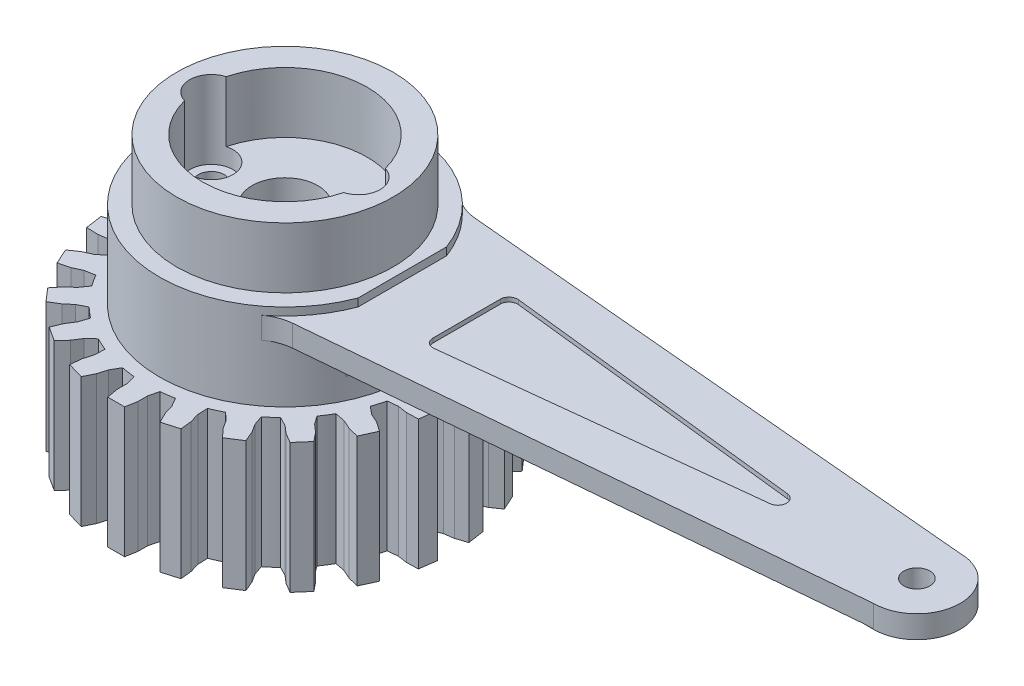
SolidWorks part; units mm, degrees
other "Markup1"
sketch "Sketch11" plane through (-17.3474, -40, -17.5082) normal (-0.1763, -0.9804, -0.0883) x (-0.1909, 0.1221, -0.974)
ref_plane "Front Plane" through (0, 0, 0) normal (0, 0, 1) x (1, 0, 0)
ref_plane "Top Plane" through (0, 0, 0) normal (0, 1, 0) x (1, 0, 0)
ref_plane "Right Plane" through (0, 0, 0) normal (1, 0, 0) x (0, 0, -1)
sketch "Sketch1" plane through (0, 0, 0) normal (0, 1, 0) x (1, 0, 0)
  circle A0 centre (0, 0) radius 14.5
extrude "Boss-Extrude1" add sketch "Sketch1" along normal blind 2 contours A0
sketch "Sketch2" plane through (0, 2, 0) normal (0, 1, 0) x (1, 0, 0)
  line L0 (0, 0) -> (-8.5, 0) construction
  line L1 (0, 0) -> (0, -2.0986) construction
  circle A0 centre (0, 0) radius 3.8
  circle A1 centre (-8.5, 0) radius 1.5
  circle A2 centre (8.5, 0) radius 1.5
  dimension "D1" = 8.5
extrude "Cut-Extrude1" cut sketch "Sketch2" against normal blind 2.5
sketch "Sketch3" plane through (0, 0, 0) normal (0, -1, 0) x (1, 0, 0)
  circle A0 centre (0, 0) radius 14.5
  circle A1 centre (0, 0) radius 12.5
  circle M3 centre (8.5, 0) radius 1.5
  circle M4 centre (-8.5, 0) radius 1.5
  circle M5 centre (0, 0) radius 3.8
  dimension "D1" = 2
extrude "Boss-Extrude2" add sketch "Sketch3" along normal blind 7 contours A1 M3 M5 M4 | A0 region at (-12.1464, 0, 0)
sketch "Sketch4" plane through (0, 2, 0) normal (0, 1, 0) x (1, 0, 0)
  circle A0 centre (0, 0) radius 3.8
  circle A1 centre (8.5, 0) radius 1.5
  circle A2 centre (-8.5, 0) radius 1.5
  circle A3 centre (0, 0) radius 14.5
extrude "Boss-Extrude3" add sketch "Sketch4" along normal blind 1 contours A3 | A2 | A1 | A0
sketch "Sketch5" plane through (0, 3, 0) normal (0, 1, 0) x (1, 0, 0)
  line L0 (0, 0) -> (0, 9.3425) construction
  circle A0 centre (8.5, 0) radius 2.6
  circle A1 centre (-8.5, 0) radius 2.5
extrude "Cut-Extrude2" cut sketch "Sketch5" against normal blind 2
sketch "Sketch6" plane through (0, 3, 0) normal (0, 1, 0) x (1, 0, 0)
  line L0 (0, 0) -> (30, 0) construction
  line L1 (30, 0) -> (45, 0) construction
  line L2 (45, 0) -> (60, 0) construction
  line L3 (60, 5) -> (13.6107, 5)
  line L4 (60, -5) -> (13.6107, -5)
  line L5 (60, 0) -> (73, 0) construction
  line L6 (60, 5) -> (70, 5)
  line L7 (60, -5) -> (70, -5)
  line L8 (70, 5) -> (73, 5)
  line L9 (70, -5) -> (73, -5)
  circle A4 centre (0, 0) radius 14.5 construction
  circle A6 centre (73, 0) radius 1.5
  arc A8 (73, -5) -> (73, 5) centre (73, 0) ccw
  circle M3 centre (0, 0) radius 14.5
  dimension "D1" = 15
  dimension "D2" = 15
  dimension "D3" = 30
  dimension "D4" = 13
extrude "Boss-Extrude4" add sketch "Sketch6" against normal blind 3.5 contours L4 L3 M3 region at (45.2639, 3, 0)
sketch "Sketch9" plane through (0, -7, 0) normal (0, -1, 0) x (-1, 0, 0)
  line L0 (0, 15.9926) -> (0, 19.4946) construction
  line L1 (0.9773, 19.4946) -> (-0.9773, 19.4946)
  line L2 (-0.9773, 19.4946) -> (-1.2082, 18.1848)
  line L45 (-0.9773, 19.4946) -> (-0.9773, 18.0837) construction
  line L46 (-1.2082, 18.1848) -> (-1.2082, 17.0658)
  line L47 (-1.2082, 17.0658) -> (-1.4932, 15.9228)
  line L48 (-1.2082, 17.0658) -> (-1.2082, 16.2048) construction
  line L49 (1.2082, 17.0658) -> (1.4932, 15.9228)
  line L50 (1.2082, 18.1848) -> (1.2082, 17.0658)
  line L51 (0.9773, 19.4946) -> (1.2082, 18.1848)
  line L52 (5.9673, 16.0341) -> (5.9187, 14.8571)
  line L53 (6.2825, 17.1078) -> (5.9673, 16.0341)
  line L54 (6.4299, 18.4296) -> (6.2825, 17.1078)
  line L55 (6.4299, 18.4296) -> (4.5546, 18.9802)
  line L56 (4.5546, 18.9802) -> (3.964, 17.7886)
  line L57 (3.964, 17.7886) -> (3.6487, 16.7149)
  line L58 (3.6487, 16.7149) -> (3.0533, 15.6985)
  line L59 (10.2429, 13.7034) -> (9.8646, 12.5878)
  line L60 (10.8478, 14.6448) -> (10.2429, 13.7034)
  line L61 (11.3617, 15.8715) -> (10.8478, 14.6448)
  line L62 (11.3617, 15.8715) -> (9.7174, 16.9282)
  line L63 (9.7174, 16.9282) -> (8.815, 15.9512)
  line L64 (8.815, 15.9512) -> (8.21, 15.0098)
  line L65 (8.21, 15.0098) -> (7.3523, 14.2024)
  line L66 (13.6887, 10.2626) -> (13.0115, 9.2987)
  line L67 (14.5343, 10.9954) -> (13.6887, 10.2626)
  line L68 (15.373, 12.0277) -> (14.5343, 10.9954)
  line L69 (15.373, 12.0277) -> (14.093, 13.5048)
  line L70 (14.093, 13.5048) -> (12.9519, 12.8216)
  line L71 (12.9519, 12.8216) -> (12.1062, 12.0888)
  line L72 (12.1062, 12.0888) -> (11.0558, 11.5557)
  line L73 (16.0255, 5.9904) -> (15.1042, 5.2563)
  line L74 (17.0434, 6.4552) -> (16.0255, 5.9904)
  line L75 (18.1389, 7.2094) -> (17.0434, 6.4552)
  line L76 (18.1389, 7.2094) -> (17.3269, 8.9873)
  line L77 (17.3269, 8.9873) -> (16.0395, 8.6533)
  line L78 (16.0395, 8.6533) -> (15.0217, 8.1884)
  line L79 (15.0217, 8.1884) -> (13.8636, 7.9728)
  line L80 (17.064, 1.2328) -> (15.9732, 0.7881)
  line L81 (18.1716, 1.3921) -> (17.064, 1.2328)
  line L82 (19.4352, 1.8071) -> (18.1716, 1.3921)
  line L83 (19.4352, 1.8071) -> (19.1571, 3.7417)
  line L84 (19.1571, 3.7417) -> (17.8277, 3.7839)
  line L85 (17.8277, 3.7839) -> (16.7201, 3.6246)
  line L86 (16.7201, 3.6246) -> (15.5482, 3.744)
  line L87 (16.7201, -3.6246) -> (15.5482, -3.744)
  line L88 (17.8277, -3.7839) -> (16.7201, -3.6246)
  line L89 (19.1571, -3.7417) -> (17.8277, -3.7839)
  line L90 (19.1571, -3.7417) -> (19.4352, -1.8071)
  line L91 (19.4352, -1.8071) -> (18.1716, -1.3921)
  line L92 (18.1716, -1.3921) -> (17.064, -1.2328)
  line L93 (17.064, -1.2328) -> (15.9732, -0.7881)
  line L94 (15.0217, -8.1884) -> (13.8636, -7.9728)
  line L95 (16.0395, -8.6533) -> (15.0217, -8.1884)
  line L96 (17.3269, -8.9873) -> (16.0395, -8.6533)
  line L97 (17.3269, -8.9873) -> (18.1389, -7.2094)
  line L98 (18.1389, -7.2094) -> (17.0434, -6.4552)
  line L99 (17.0434, -6.4552) -> (16.0255, -5.9904)
  line L100 (16.0255, -5.9904) -> (15.1042, -5.2563)
  line L101 (12.1062, -12.0888) -> (11.0558, -11.5557)
  line L102 (12.9519, -12.8216) -> (12.1062, -12.0888)
  line L103 (14.093, -13.5048) -> (12.9519, -12.8216)
  line L104 (14.093, -13.5048) -> (15.373, -12.0277)
  line L105 (15.373, -12.0277) -> (14.5343, -10.9954)
  line L106 (14.5343, -10.9954) -> (13.6887, -10.2626)
  line L107 (13.6887, -10.2626) -> (13.0115, -9.2987)
  line L108 (8.21, -15.0098) -> (7.3523, -14.2024)
  line L109 (8.815, -15.9512) -> (8.21, -15.0098)
  line L110 (9.7174, -16.9282) -> (8.815, -15.9512)
  line L111 (9.7174, -16.9282) -> (11.3617, -15.8715)
  line L112 (11.3617, -15.8715) -> (10.8478, -14.6448)
  line L113 (10.8478, -14.6448) -> (10.2429, -13.7034)
  line L114 (10.2429, -13.7034) -> (9.8646, -12.5878)
  line L115 (3.6487, -16.7149) -> (3.0533, -15.6985)
  line L116 (3.964, -17.7886) -> (3.6487, -16.7149)
  line L117 (4.5546, -18.9802) -> (3.964, -17.7886)
  line L118 (4.5546, -18.9802) -> (6.4299, -18.4296)
  line L119 (6.4299, -18.4296) -> (6.2825, -17.1078)
  line L120 (6.2825, -17.1078) -> (5.9673, -16.0341)
  line L121 (5.9673, -16.0341) -> (5.9187, -14.8571)
  line L122 (-1.2082, -17.0658) -> (-1.4932, -15.9228)
  line L123 (-1.2082, -18.1848) -> (-1.2082, -17.0658)
  line L124 (-0.9773, -19.4946) -> (-1.2082, -18.1848)
  line L125 (-0.9773, -19.4946) -> (0.9773, -19.4946)
  line L126 (0.9773, -19.4946) -> (1.2082, -18.1848)
  line L127 (1.2082, -18.1848) -> (1.2082, -17.0658)
  line L128 (1.2082, -17.0658) -> (1.4932, -15.9228)
  line L129 (-5.9673, -16.0341) -> (-5.9187, -14.8571)
  line L130 (-6.2825, -17.1078) -> (-5.9673, -16.0341)
  line L131 (-6.4299, -18.4296) -> (-6.2825, -17.1078)
  line L132 (-6.4299, -18.4296) -> (-4.5546, -18.9802)
  line L133 (-4.5546, -18.9802) -> (-3.964, -17.7886)
  line L134 (-3.964, -17.7886) -> (-3.6487, -16.7149)
  line L135 (-3.6487, -16.7149) -> (-3.0533, -15.6985)
  line L136 (-10.2429, -13.7034) -> (-9.8646, -12.5878)
  line L137 (-10.8478, -14.6448) -> (-10.2429, -13.7034)
  line L138 (-11.3617, -15.8715) -> (-10.8478, -14.6448)
  line L139 (-11.3617, -15.8715) -> (-9.7174, -16.9282)
  line L140 (-9.7174, -16.9282) -> (-8.815, -15.9512)
  line L141 (-8.815, -15.9512) -> (-8.21, -15.0098)
  line L142 (-8.21, -15.0098) -> (-7.3523, -14.2024)
  line L143 (-13.6887, -10.2626) -> (-13.0115, -9.2987)
  line L144 (-14.5343, -10.9954) -> (-13.6887, -10.2626)
  line L145 (-15.373, -12.0277) -> (-14.5343, -10.9954)
  line L146 (-15.373, -12.0277) -> (-14.093, -13.5048)
  line L147 (-14.093, -13.5048) -> (-12.9519, -12.8216)
  line L148 (-12.9519, -12.8216) -> (-12.1062, -12.0888)
  line L149 (-12.1062, -12.0888) -> (-11.0558, -11.5557)
  line L150 (-16.0255, -5.9904) -> (-15.1042, -5.2563)
  line L151 (-17.0434, -6.4552) -> (-16.0255, -5.9904)
  line L152 (-18.1389, -7.2094) -> (-17.0434, -6.4552)
  line L153 (-18.1389, -7.2094) -> (-17.3269, -8.9873)
  line L154 (-17.3269, -8.9873) -> (-16.0395, -8.6533)
  line L155 (-16.0395, -8.6533) -> (-15.0217, -8.1884)
  line L156 (-15.0217, -8.1884) -> (-13.8636, -7.9728)
  line L157 (-17.064, -1.2328) -> (-15.9732, -0.7881)
  line L158 (-18.1716, -1.3921) -> (-17.064, -1.2328)
  line L159 (-19.4352, -1.8071) -> (-18.1716, -1.3921)
  line L160 (-19.4352, -1.8071) -> (-19.1571, -3.7417)
  line L161 (-19.1571, -3.7417) -> (-17.8277, -3.7839)
  line L162 (-17.8277, -3.7839) -> (-16.7201, -3.6246)
  line L163 (-16.7201, -3.6246) -> (-15.5482, -3.744)
  line L164 (-16.7201, 3.6246) -> (-15.5482, 3.744)
  line L165 (-17.8277, 3.7839) -> (-16.7201, 3.6246)
  line L166 (-19.1571, 3.7417) -> (-17.8277, 3.7839)
  line L167 (-19.1571, 3.7417) -> (-19.4352, 1.8071)
  line L168 (-19.4352, 1.8071) -> (-18.1716, 1.3921)
  line L169 (-18.1716, 1.3921) -> (-17.064, 1.2328)
  line L170 (-17.064, 1.2328) -> (-15.9732, 0.7881)
  line L171 (-15.0217, 8.1884) -> (-13.8636, 7.9728)
  line L172 (-16.0395, 8.6533) -> (-15.0217, 8.1884)
  line L173 (-17.3269, 8.9873) -> (-16.0395, 8.6533)
  line L174 (-17.3269, 8.9873) -> (-18.1389, 7.2094)
  line L175 (-18.1389, 7.2094) -> (-17.0434, 6.4552)
  line L176 (-17.0434, 6.4552) -> (-16.0255, 5.9904)
  line L177 (-16.0255, 5.9904) -> (-15.1042, 5.2563)
  line L178 (-12.1062, 12.0888) -> (-11.0558, 11.5557)
  line L179 (-12.9519, 12.8216) -> (-12.1062, 12.0888)
  line L180 (-14.093, 13.5048) -> (-12.9519, 12.8216)
  line L181 (-14.093, 13.5048) -> (-15.373, 12.0277)
  line L182 (-15.373, 12.0277) -> (-14.5343, 10.9954)
  line L183 (-14.5343, 10.9954) -> (-13.6887, 10.2626)
  line L184 (-13.6887, 10.2626) -> (-13.0115, 9.2987)
  line L185 (-8.21, 15.0098) -> (-7.3523, 14.2024)
  line L186 (-8.815, 15.9512) -> (-8.21, 15.0098)
  line L187 (-9.7174, 16.9282) -> (-8.815, 15.9512)
  line L188 (-9.7174, 16.9282) -> (-11.3617, 15.8715)
  line L189 (-11.3617, 15.8715) -> (-10.8478, 14.6448)
  line L190 (-10.8478, 14.6448) -> (-10.2429, 13.7034)
  line L191 (-10.2429, 13.7034) -> (-9.8646, 12.5878)
  line L192 (-3.6487, 16.7149) -> (-3.0533, 15.6985)
  line L193 (-3.964, 17.7886) -> (-3.6487, 16.7149)
  line L194 (-4.5546, 18.9802) -> (-3.964, 17.7886)
  line L195 (-4.5546, 18.9802) -> (-6.4299, 18.4296)
  line L196 (-6.4299, 18.4296) -> (-6.2825, 17.1078)
  line L197 (-6.2825, 17.1078) -> (-5.9673, 16.0341)
  line L198 (-5.9673, 16.0341) -> (-5.9187, 14.8571)
  arc A2 (-9.8646, 12.5878) -> (-11.0558, 11.5557) centre (0, 0) ccw
  arc A17 (-13.0115, 9.2987) -> (-13.8636, 7.9728) centre (0, 0) ccw
  circle A18 centre (0, 0) radius 20
  arc A19 (-5.9187, 14.8571) -> (-7.3523, 14.2024) centre (0, 0) ccw
  arc A20 (-1.4932, 15.9228) -> (-3.0533, 15.6985) centre (0, 0) ccw
  arc A21 (3.0533, 15.6985) -> (1.4932, 15.9228) centre (0, 0) ccw
  arc A22 (7.3523, 14.2024) -> (5.9187, 14.8571) centre (0, 0) ccw
  arc A23 (11.0558, 11.5557) -> (9.8646, 12.5878) centre (0, 0) ccw
  arc A24 (13.8636, 7.9728) -> (13.0115, 9.2987) centre (0, 0) ccw
  arc A25 (15.5482, 3.744) -> (15.1042, 5.2563) centre (0, 0) ccw
  arc A26 (15.9732, -0.7881) -> (15.9732, 0.7881) centre (0, 0) ccw
  arc A27 (15.1042, -5.2563) -> (15.5482, -3.744) centre (0, 0) ccw
  arc A28 (13.0115, -9.2987) -> (13.8636, -7.9728) centre (0, 0) ccw
  arc A29 (9.8646, -12.5878) -> (11.0558, -11.5557) centre (0, 0) ccw
  arc A30 (5.9187, -14.8571) -> (7.3523, -14.2024) centre (0, 0) ccw
  arc A31 (1.4932, -15.9228) -> (3.0533, -15.6985) centre (0, 0) ccw
  arc A32 (-3.0533, -15.6985) -> (-1.4932, -15.9228) centre (0, 0) ccw
  arc A33 (-7.3523, -14.2024) -> (-5.9187, -14.8571) centre (0, 0) ccw
  arc A34 (-11.0558, -11.5557) -> (-9.8646, -12.5878) centre (0, 0) ccw
  arc A35 (-13.8636, -7.9728) -> (-13.0115, -9.2987) centre (0, 0) ccw
  arc A36 (-15.5482, -3.744) -> (-15.1042, -5.2563) centre (0, 0) ccw
  arc A37 (-15.9732, 0.7881) -> (-15.9732, -0.7881) centre (0, 0) ccw
  arc A38 (-15.1042, 5.2563) -> (-15.5482, 3.744) centre (0, 0) ccw
  circle A39 centre (0, 0) radius 12.5
  point P188 (0, 0)
  dimension "D2" = 1.33
  dimension "D1" = 10
  dimension "D3" = 1.119
  dimension "D5" = 1.178
  dimension "D4" = 14
  dimension "D6" = 22
extrude "Boss-Extrude5" add sketch "Sketch9" along normal blind 30 contours L184 A17 L171 L172 L173 L174 L175 L176 L177 A38 L164 L165 L166 L167 L168 L169 L170 A37 L157 L158 L159 L160 L161 L162 L163 A36 L150 L151 L152 L153 L154 L155 L156 A35 L143 L144 L145 L146 L147 L148 L149 A34 L136 L137 L138 L139 L140 L141 L142 A33 L129 L130 L131 L132 L133 L134 L135 A32 L122 L123 L124 L125 L126 L127 L128 A31 L115 L116 L117 L118 L119 L120 L121 A30 L108 L109 L110 L111 L112 L113 L114 A29 L101 L102 L103 L104 L105 L106 L107 A28 L94 L95 L96 L97 L98 L99 L100 A27 L87 L88 L89 L90 L91 L92 L93 A26 L80 L81 L82 L83 L84 L85 L86 A25 L73 L74 L75 L76 L77 L78 L79 A24 L66 L67 L68 L69 L70 L71 L72 A23 L59 L60 L61 L62 L63 L64 L65 A22 L52 L53 L54 L55 L56 L57 L58 A21 L49 L50 L51 L1 L2 L46 L47 A20 L192 L193 L194 L195 L196 L197 L198 A19 L185 L186 L187 L188 L189 L190 L191 A2 L178 L179 L180 L181 L182 L183 | A39
sketch "Sketch15" plane through (0, 3, 0) normal (0, 1, 0) x (1, 0, 0)
  circle A0 centre (0, 0) radius 12.5
  circle A2 centre (0, 0) radius 9.5
  dimension "D1" = 3
extrude "Boss-Extrude9" add sketch "Sketch15" along normal blind 7 contours A0 | A2
sketch "Sketch17" plane through (0, 10, 0) normal (0, 1, 0) x (1, 0, 0)
  line L0 (0, 0) -> (-8.5, 0) construction
  line L1 (0, 0) -> (0, -2.0291) construction
  circle A0 centre (-8.5, 0) radius 2.5
  circle A1 centre (8.5, 0) radius 2.5
  dimension "D1" = 8.5
extrude "Cut-Extrude5" cut sketch "Sketch17" against normal blind 7
sketch "Sketch18" plane through (0, 3, 0) normal (0, 1, 0) x (1, 0, 0)
  line L1 (13.5686, 6.8144) -> (85.2134, 6.8144)
  line L2 (13.5686, 6.8144) -> (13.5686, -6.7184)
  line L3 (13.5686, -6.7184) -> (85.2134, -6.7184)
  line L4 (85.2134, 6.8144) -> (85.2134, -6.7184)
extrude "Cut-Extrude6" cut sketch "Sketch18" against normal blind 0.9
sketch "Sketch19" plane through (0, -37, 0) normal (0, -1, 0) x (1, 0, 0)
  line L1 (-30.1927, 29.9961) -> (31.3867, 29.9961)
  line L2 (-30.1927, 29.9961) -> (-30.1927, -24.9381)
  line L3 (-30.1927, -24.9381) -> (31.3867, -24.9381)
  line L4 (31.3867, 29.9961) -> (31.3867, -24.9381)
extrude "Cut-Extrude7" cut sketch "Sketch19" against normal blind 15
sketch "Sketch20" plane through (0, 2.1, 0) normal (0, 1, 0) x (1, 0, 0)
  line L0 (13.5686, 0) -> (46.2278, 0) construction
  line L1 (13.5686, 5.1131) -> (13.5686, -5.1131) construction
  line L3 (73, 5) -> (9.8263, 10.6628)
  line L4 (73, 5) -> (13.5686, 4.68)
  line L5 (13.5686, 4.68) -> (13.5686, 5.1131)
  line L6 (73, -5) -> (13.5686, -4.68)
  line L7 (73, -5) -> (9.8263, -10.6628)
  line L8 (13.5686, -4.68) -> (13.5686, -5.1131)
  circle A0 centre (0, 0) radius 14.5 construction
  arc A1 (13.5686, 5.1131) -> (9.8263, 10.6628) centre (0, 0) ccw
  arc A2 (13.5686, -5.1131) -> (9.8263, -10.6628) centre (0, 0) cw
extrude "Boss-Extrude14" add sketch "Sketch20" against normal blind 2.5 contours L5 A1 L3 L4 | L6 L8 A2 L7
fillet "Fillet2" radius 5 2 edges at (9.8263, 0.85, -10.6628) (9.8263, 0.85, 10.6628)
sketch "Sketch21" plane through (0, -0.5, 0) normal (0, -1, 0) x (1, 0, 0)
  line L0 (13.6107, 5) -> (73, 5) construction
  line L1 (13.6107, 5) -> (54.7559, 5)
  line L2 (13.6107, 5) -> (13.6107, -5)
  line L3 (13.6107, -5) -> (54.7559, -5)
  line L4 (54.7559, 5) -> (54.7559, -5)
  line L5 (73, -5) -> (13.6107, -5) construction
extrude "Boss-Extrude15" add sketch "Sketch21" along normal blind 4
sketch "Sketch22" plane through (0, 0, 5) normal (0, 0, 1) x (1, 0, 0)
  line L0 (13.6107, -4.5) -> (54.7559, -0.5)
  line L1 (54.7559, -0.5) -> (54.7559, -4.5)
  line L2 (54.7559, -4.5) -> (13.6107, -4.5)
extrude "Cut-Extrude8" cut sketch "Sketch22" against normal blind 17
fillet "Fillet5" radius 2 2 edges at (13.6107, -2.45, 5) (13.6107, -2.45, -5)
sketch "Sketch23" plane through (0, 2.1, 0) normal (0, 1, 0) x (1, 0, 0)
  line L0 (73, 0) -> (66, 0) construction
  line L1 (66, 0) -> (21, 0) construction
  line L2 (21, 5) -> (21, -5)
  line L3 (21, -5) -> (66, 0)
  line L4 (21, 5) -> (66, 0)
  dimension "D1" = 7
  dimension "D2" = 45
  dimension "D3" = 5
extrude "Cut-Extrude9" cut sketch "Sketch23" against normal blind 0.5
fillet "Fillet6" radius 1 3 edges at (21, 1.85, 5) (21, 1.85, -5) (66, 1.85, 0)
